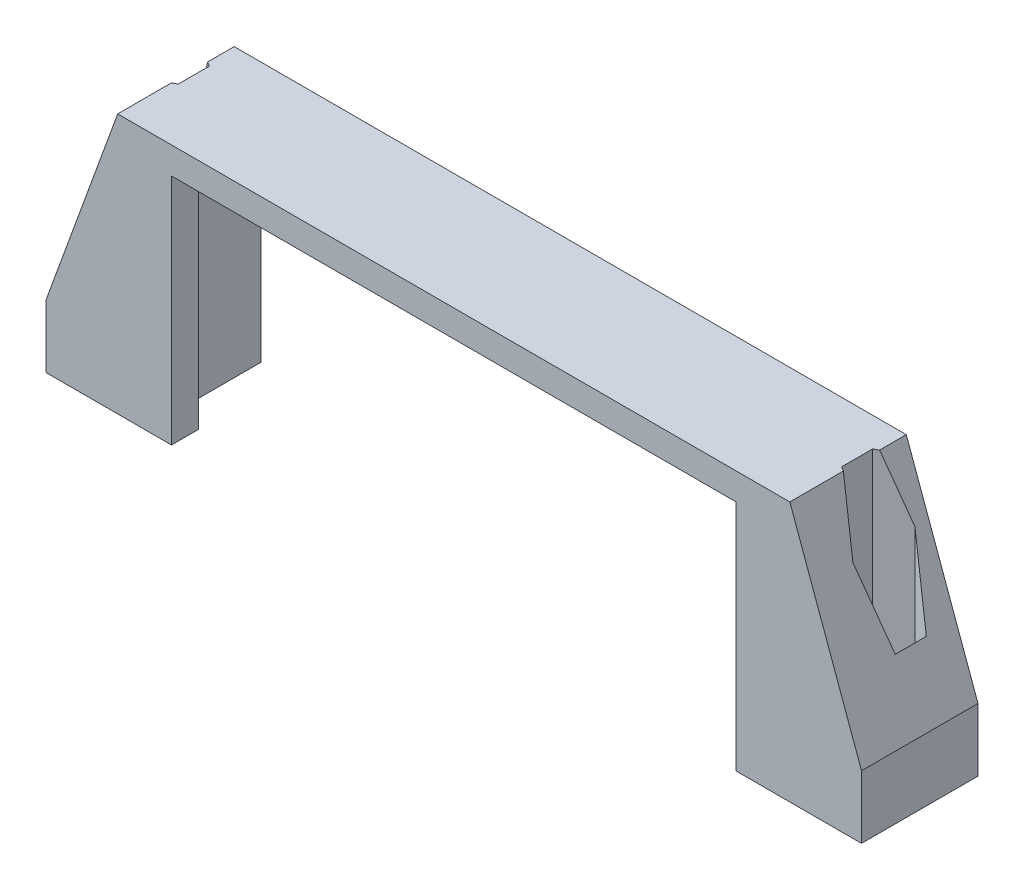
SolidWorks part; units mm, degrees
material "PET"
ref_plane "Front Plane" through (0, 0, 0) normal (0, 0, 1) x (1, 0, 0)
ref_plane "Top Plane" through (0, 0, 0) normal (0, 1, 0) x (1, 0, 0)
ref_plane "Right Plane" through (0, 0, 0) normal (1, 0, 0) x (0, 0, -1)
sketch "Sketch1" plane through (0, 0, 0) normal (0, 0, 1) x (1, 0, 0)
  line L0 (-34.5, 0) -> (34.5, 0) construction
  line L1 (0, 0) -> (0, 26) construction
  line L2 (0, 26) -> (34.5, 26)
  line L3 (34.5, 26) -> (34.5, 0)
  line L4 (34.5, 0) -> (45.5, 0)
  line L5 (45.5, 0) -> (45.5, 7.0202)
  line L6 (45.5, 7.0202) -> (37.5, 29)
  line L7 (37.5, 29) -> (0, 29)
  line L8 (0, 29) -> (0, 26)
  dimension "D1" = 69
  dimension "D2" = 26
  dimension "D3" = 11
  dimension "D4" = 3
  dimension "D5" = 3
  dimension "D6" = 20
extrude "Boss-Extrude1" add sketch "Sketch1" along normal blind 10
ref_plane "Plane1" through (0, 7.0202, 0) normal (0, 1, 0) x (1, 0, 0)
sketch "Sketch2" plane through (0, 7.0202, 0) normal (0, 1, 0) x (1, 0, 0)
  line L0 (40, -10) -> (40, 0) construction
  line L1 (34.5, -10) -> (45.5, -10) construction
  line L2 (34.5, 0) -> (45.5, 0) construction
  line L3 (34.5, -5) -> (45.5, -5) construction
  line L4 (34.5, -10) -> (34.5, 0) construction
  line L5 (45.5, -10) -> (45.5, 0) construction
  line L7 (40, -8.4641) -> (43, -6.7321)
  line L8 (43, -6.7321) -> (43, -3.2679)
  line L9 (43, -3.2679) -> (40, -1.5359)
  line L10 (40, -1.5359) -> (37, -3.2679)
  line L11 (37, -3.2679) -> (37, -6.7321)
  line L12 (37, -6.7321) -> (40, -8.4641)
  circle A0 centre (40, -5) radius 1.85
  circle A1 centre (40, -5) radius 3 construction
  dimension "D1" = 3.7
  dimension "D2" = 6
extrude "Cut-Extrude1" cut sketch "Sketch2" along normal blind 40 contours A0 | L11 L12 L7 L8 L9 L10 A0 region at (38.5458, 7.0202, 7.5187) region at (40, 7.0202, 5)
extrude "Cut-Extrude2" cut sketch "Sketch2<3>" against normal blind 40 contours A0 region at (40, 7.0202, 5)
sketch "Sketch2<3>" plane through (0, 7.0202, 0) normal (0, 1, 0) x (1, 0, 0) same geometry as "Sketch2"
mirror "Mirror1" about plane through (0, 29, 10) normal (1, 0, 0) of bodies 104 101
sketch "Sketch3" plane through (0, 0, 10) normal (0, 0, 1) x (1, 0, 0)
  line L0 (-34.5, 26) -> (34.5, 26) construction
  line L1 (-34.5, 26) -> (-34.5, 0) construction
  line L2 (34.5, 26) -> (34.5, 0) construction
  line L10 (34.5, 0) -> (45.5, 0)
  line L11 (45.5, 0) -> (45.5, 7.0202)
  line L12 (45.5, 7.0202) -> (37.5, 29)
  line L13 (37.5, 29) -> (-37.5, 29)
  line L14 (-37.5, 29) -> (-45.5, 7.0202)
  line L15 (-45.5, 7.0202) -> (-45.5, 0)
  line L16 (-45.5, 0) -> (-34.5, 0)
  line L17 (-34.5, 0) -> (-34.5, 26)
  line L18 (-34.5, 26) -> (34.5, 26)
  line L19 (34.5, 26) -> (34.5, 0)
  line L20 (31.5, 0) -> (45.5, 0)
  line L21 (45.5, 0) -> (45.5, 7.0202)
  line L22 (45.5, 7.0202) -> (37.5, 29)
  line L23 (37.5, 29) -> (-37.5, 29)
  line L24 (-37.5, 29) -> (-45.5, 7.0202)
  line L25 (-45.5, 7.0202) -> (-45.5, 0)
  line L26 (-45.5, 0) -> (-31.5, 0)
  line L27 (-31.5, 0) -> (-31.5, 26)
  line L28 (-31.5, 26) -> (31.5, 26)
  line L29 (31.5, 26) -> (31.5, 0)
  dimension "D2" = 3
  dimension "D3" = 3
  dimension "D1" = 0
extrude "Boss-Extrude2" add sketch "Sketch3" along normal blind 3
